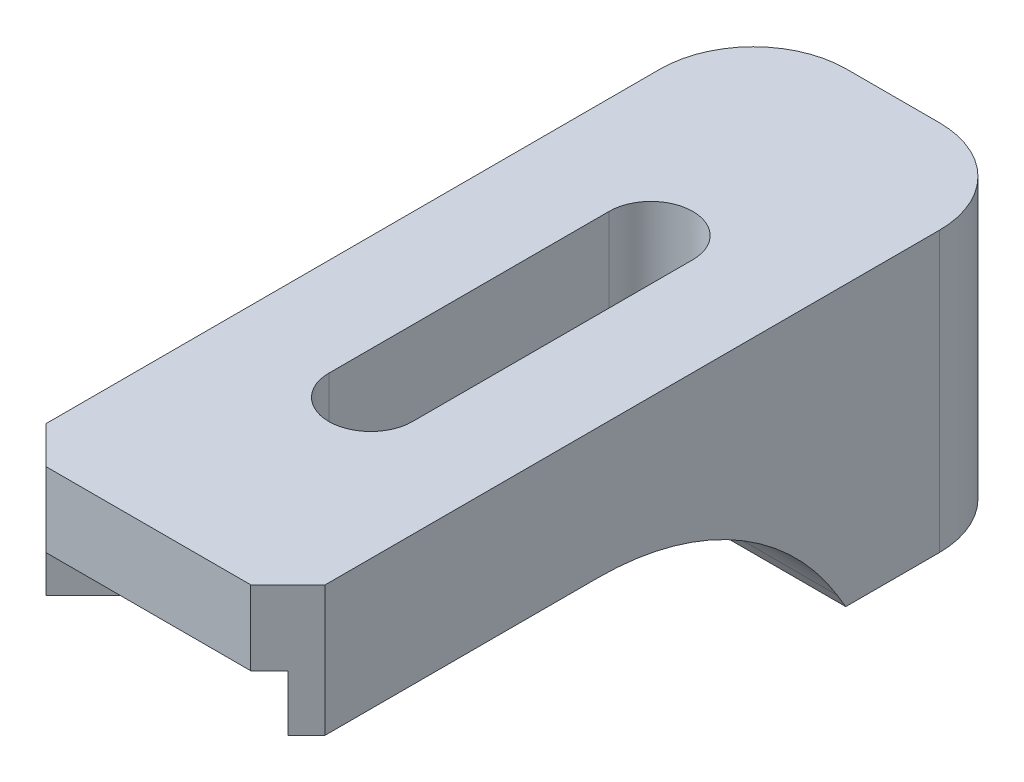
SolidWorks part; units mm, degrees
ref_plane "Front Plane" through (0, 0, 0) normal (0, 0, 1) x (1, 0, 0)
ref_plane "Top Plane" through (0, 0, 0) normal (0, 1, 0) x (1, 0, 0)
ref_plane "Right Plane" through (0, 0, 0) normal (1, 0, 0) x (0, 0, -1)
sketch "Sketch1" plane through (0, 0, 0) normal (0, 1, 0) x (1, 0, 0)
  line L1 (-7.5, -20) -> (7.5, -20)
  line L2 (-7.5, -20) -> (-7.5, 20)
  line L3 (-7.5, 20) -> (7.5, 20)
  line L4 (7.5, -20) -> (7.5, 20)
  line L5 (-7.5, -20) -> (7.5, 20) construction
  line L6 (-7.5, 20) -> (7.5, -20) construction
  point P0 (0, 0)
  dimension "D1" = 40
  dimension "D2" = 15
extrude "Boss-Extrude1" add sketch "Sketch1" along normal blind 15
sketch "Sketch3" plane through (-7.5, 0, 0) normal (-1, 0, 0) x (0, 0, 1)
  line L0 (20, 0) -> (20, 8)
  line L1 (20, 15) -> (20, 0) construction
  line L2 (20, 8) -> (-5.1215, 8)
  line L3 (-5.1215, 8) -> (-9.9682, 0)
  line L4 (-20, 0) -> (20, 0) construction
  line L5 (-9.9682, 0) -> (20, 0)
  dimension "D1" = 8
extrude "Cut-Extrude1" cut sketch "Sketch3" against normal through all contours L3 L5 L0 L2
fillet "Fillet1" radius 15 1 edges at (0, 8, -5.1215)
sketch "Sketch5" plane through (0, 8, 0) normal (0, -1, 0) x (1, 0, 0)
  line L0 (7.5, 20) -> (0.6817, 13.1817)
  line L1 (-0.6817, 13.1817) -> (-7.5, 20)
  line L2 (-7.5, 20) -> (7.5, 20)
  arc A0 (-0.6817, 13.1817) -> (0.6817, 13.1817) centre (0, 12.5) ccw
  dimension "D1" = 0.964
extrude "Cut-Extrude2" cut sketch "Sketch5" against normal blind 3 contours L0 A0 L1 L2
fillet "Fillet2" radius 0.5 2 edges at (0.6817, 9.5, 13.1817) (-0.6817, 9.5, 13.1817)
fillet "Fillet4" radius 0.5 2 edges at (7.5, 9.5, 20) (-7.5, 9.5, 20) tangent propagation no
chamfer "Chamfer1" distance 2 angle 45 2 edges at (7.5, 13, 20) (-7.5, 13, 20)
fillet "Fillet6" radius 5 2 edges at (7.5, 7.5, -20) (-7.5, 7.5, -20)
sketch "Sketch6" plane through (0, 15, 0) normal (0, 1, 0) x (1, 0, 0)
  line L0 (0, 0) -> (0, -8.0565) construction
  line L1 (0, 0) -> (0, 7) construction
  line L2 (-2.25, 7) -> (-2.25, -8.0565)
  line L4 (2.25, -8.0565) -> (2.25, 7)
  arc A0 (2.25, 7) -> (-2.25, 7) centre (0, 7) ccw
  arc A1 (-2.25, -8.0565) -> (2.25, -8.0565) centre (0, -8.0565) ccw
  point P3 (0, 0)
  dimension "D1" = 7
extrude "Cut-Extrude3" cut sketch "Sketch6" against normal through all
